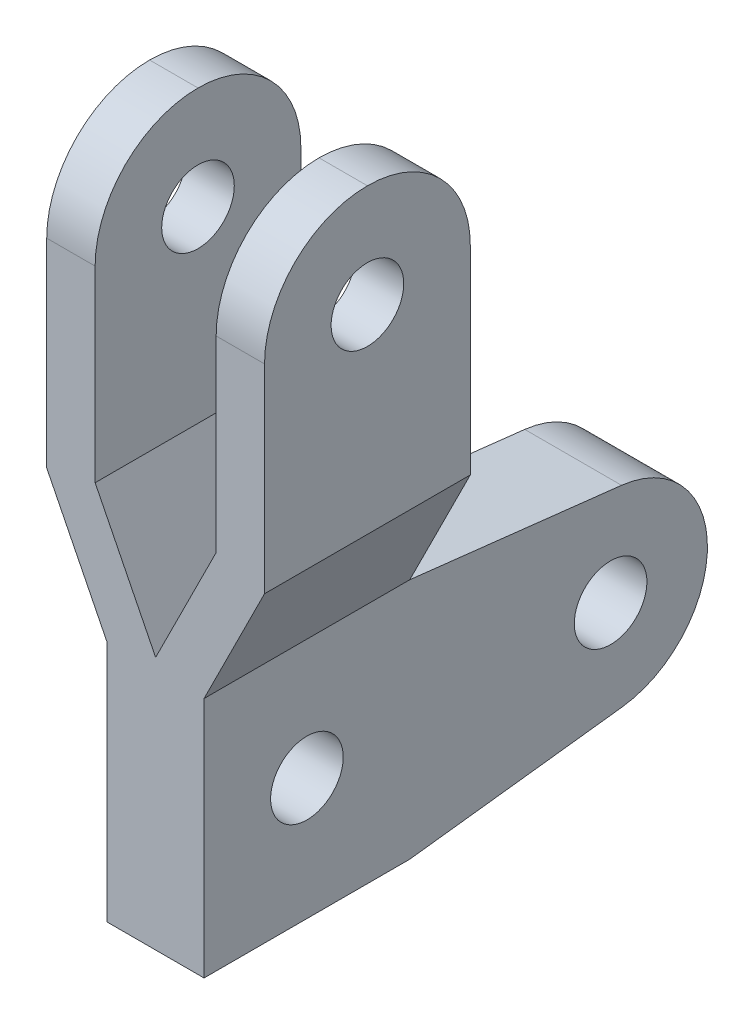
SolidWorks part; units mm, degrees
ref_plane "Plane1" through (0, 0, 0) normal (0, 0, 1) x (1, 0, 0)
ref_plane "Plane2" through (0, 0, 0) normal (0, 1, 0) x (1, 0, 0)
ref_plane "Plane3" through (0, 0, 0) normal (1, 0, 0) x (0, 0, -1)
other "Configuration Table"
sketch "Sketch1" plane through (0, 0, 0) normal (0, 0, 1) x (1, 0, 0)
  line L2 (-3.175, 3.5498) -> (-5.715, 3.5498)
  line L3 (3.175, -11.6902) -> (3.175, 3.5498)
  line L4 (5.715, 3.5498) -> (5.715, -12.2899)
  line L5 (5.715, -12.2899) -> (2.54, -18.6399)
  line L6 (0, 0) -> (0, -23.5908) construction
  line L7 (0, -18.0402) -> (3.175, -11.6902)
  line L8 (2.54, -31.3399) -> (2.54, -18.6399)
  line L9 (3.175, 3.5498) -> (5.715, 3.5498)
  line L10 (-3.175, -11.6902) -> (-3.175, 3.5498)
  line L11 (-5.715, 3.5498) -> (-5.715, -12.2899)
  line L12 (-5.715, -12.2899) -> (-2.54, -18.6399)
  line L13 (0, -18.0402) -> (-3.175, -11.6902)
  line L14 (-2.54, -31.3399) -> (-2.54, -18.6399)
  line L15 (2.54, -31.3399) -> (-2.54, -31.3399)
  dimension "D1" = 5.08
  dimension "D2" = 2.54
  dimension "D3" = 2.54
  dimension "D4" = 15.24
  dimension "D5" = 12.7
  dimension "D6" = 6.35
extrude "Base-Extrude" add sketch "Sketch1" along normal blind 10.795
sketch "Sketch2" plane through (5.715, 0, 0) normal (1, 0, 0) x (0, 0, -1)
  line L0 (-10.795, 3.5498) -> (0, 3.5498) construction
  circle A0 centre (-5.3975, -1.8477) radius 1.905
  circle A1 centre (-5.3975, -1.8477) radius 1.905 construction
  point P2 (-5.3975, 3.5498)
  dimension "D1" = 5.3975
extrude "Cut-Extrude1" cut sketch "Sketch2" against normal through all
fillet "Fillet1" radius 5.3975 8 edges at (4.445, 3.5498, 0) (-4.445, 3.5498, 0) (3.175, 3.5498, 5.3975) (5.715, 3.5498, 5.3975) (-5.715, 3.5498, 5.3975) (-3.175, 3.5498, 5.3975) (4.445, 3.5498, 10.795) (-4.445, 3.5498, 10.795)
sketch "Sketch3" plane through (2.54, 0, 0) normal (1, 0, 0) x (0, 0, -1)
  line L0 (-10.795, -31.3399) -> (0, -31.3399) construction
  circle A0 centre (-5.3975, -24.9516) radius 1.905
  circle A1 centre (-5.3975, -1.8477) radius 1.905 construction
  point P4 (-5.3975, -31.3399)
  dimension "D1" = 23.1038
extrude "Cut-Extrude2" cut sketch "Sketch3" against normal through all
sketch "Sketch4" plane through (2.54, 0, 0) normal (1, 0, 0) x (0, 0, -1)
  line L0 (0, -31.3399) -> (11.1469, -29.995)
  line L1 (11.1127, -19.9041) -> (0, -18.6399)
  line L2 (0, -31.3399) -> (0, -18.6399) construction
  line L3 (0, -31.3399) -> (0, -18.6399)
  arc A0 (11.1469, -29.995) -> (11.1127, -19.9041) centre (10.5385, -24.9516) ccw
  circle A1 centre (-5.3975, -24.9516) radius 1.905 construction
  circle A2 centre (10.5385, -24.9516) radius 1.905
  point P9 (-5.3975, -24.9516)
  dimension "D1" = 15.936
  dimension "D2" = 5.08
extrude "Boss-Extrude1" add sketch "Sketch4" along normal up to surface (5.08 mm away)
